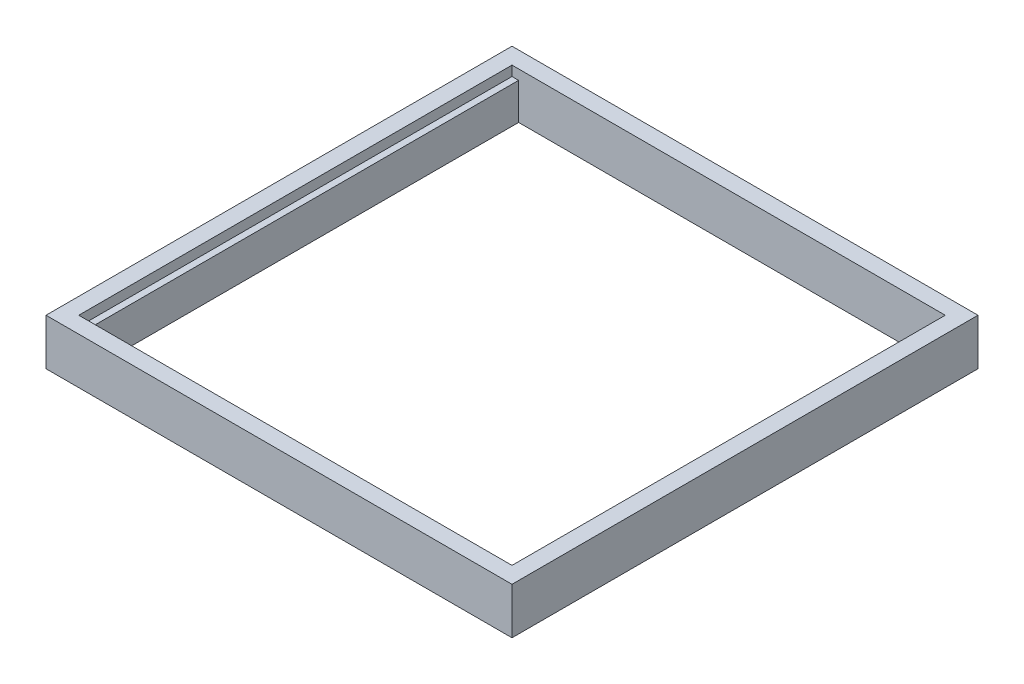
SolidWorks part; units mm, degrees
ref_plane "Front Plane" through (0, 0, 0) normal (0, 0, 1) x (1, 0, 0)
ref_plane "Top Plane" through (0, 0, 0) normal (0, 1, 0) x (1, 0, 0)
ref_plane "Right Plane" through (0, 0, 0) normal (1, 0, 0) x (0, 0, -1)
sketch "Sketch1" plane through (0, 0, 0) normal (0, 1, 0) x (1, 0, 0)
  line L1 (-37.7, -37.7) -> (37.7, -37.7)
  line L2 (-37.7, -37.7) -> (-37.7, 37.7)
  line L3 (-37.7, 37.7) -> (37.7, 37.7)
  line L4 (37.7, -37.7) -> (37.7, 37.7)
  line L5 (-37.7, -37.7) -> (37.7, 37.7) construction
  line L6 (-37.7, 37.7) -> (37.7, -37.7) construction
  point P0 (0, 0)
  dimension "D1" = 75.4
  dimension "D2" = 75.4
extrude "Base" add sketch "Sketch1" along normal blind 7.5
sketch "Sketch2" plane through (0, 7.5, 0) normal (0, 1, 0) x (1, 0, 0)
  line L0 (0, -4.125) -> (0, 4.125) construction
  line L1 (-35.05, -35.05) -> (35.05, -35.05)
  line L2 (-35.05, -35.05) -> (-35.05, 35.05)
  line L3 (-35.05, 35.05) -> (35.05, 35.05)
  line L4 (35.05, -35.05) -> (35.05, 35.05)
  line L5 (-35.05, -35.05) -> (35.05, 35.05) construction
  line L6 (-35.05, 35.05) -> (35.05, -35.05) construction
  line L7 (0, -4.125) -> (0, 4.125) construction
  point P1 (0, 0)
  dimension "D1" = 70.1
  dimension "D2" = 70.1
extrude "Slot" cut sketch "Sketch2" against normal blind 1.6
sketch "Sketch3" plane through (0, 5.9, 0) normal (0, 1, 0) x (1, 0, 0)
  line L6 (-33.9775, -35.05) -> (33.9775, -35.05)
  line L7 (-33.9775, -35.05) -> (-33.9775, 35.05)
  line L8 (-33.9775, 35.05) -> (33.9775, 35.05)
  line L9 (33.9775, -35.05) -> (33.9775, 35.05)
  line L10 (-33.9775, -35.05) -> (33.9775, 35.05) construction
  line L11 (-33.9775, 35.05) -> (33.9775, -35.05) construction
  line L12 (-35.05, 35.05) -> (35.05, -35.05) construction
  line L13 (-35.05, -35.05) -> (35.05, 35.05) construction
  line L16 (-35.05, -35.05) -> (35.05, -35.05) construction
  line L17 (35.05, 35.05) -> (-35.05, 35.05) construction
  point P2 (0, 37.5)
  point P4 (0, 0)
  point P8 (0, 0)
extrude "Slot-Components" cut sketch "Sketch3" against normal up to surface (5.9 mm away) up to face at (0, 0, 0)
